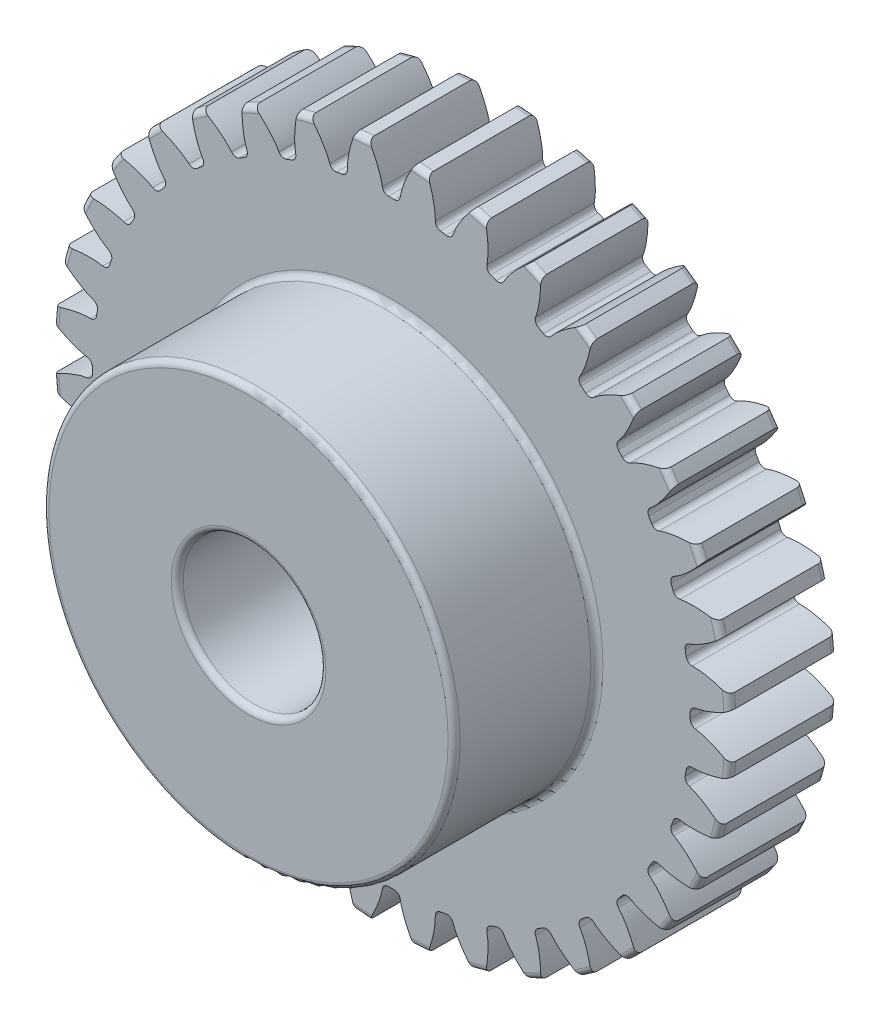
SolidWorks part; units mm, degrees
ref_plane "Front Plane" through (0, 0, 0) normal (0, 0, 1) x (1, 0, 0)
ref_plane "Top Plane" through (0, 0, 0) normal (0, 1, 0) x (1, 0, 0)
ref_plane "Right Plane" through (0, 0, 0) normal (1, 0, 0) x (0, 0, -1)
sketch "Sketch1" plane through (0, 0, 0) normal (0, 0, 1) x (1, 0, 0)
  line L0 (0, 0) -> (0, 14.2875) construction
  line L1 (-4.5919, 15.9588) -> (4.5919, 12.6162) construction
  circle A0 centre (0, 0) radius 13.2953 construction
  circle A1 centre (0, 0) radius 15.0813 construction
  circle A2 centre (0, 0) radius 14.2875 construction
  circle A3 centre (0, 0) radius 13.4259 construction
  circle A4 centre (0, 0) radius 3.175 construction
  circle A5 centre (0, 0) radius 9.144 construction
  point P8 (406.4, 0)
  point P13 (457.2, 0)
  dimension "OD | Outside Diameter" = 30.1625
  dimension "Root Diameter" = 26.5906
  dimension "Gear Pitch Diameter" = 28.575
  dimension "Base Diameter" = 26.8517
  dimension "For Shaft Diameter" = 6.35
  dimension "Hub Diameter" = 18.288
  dimension "Pressure Angle" = 20
  dimension "Number of Teeth" = 914.4
  dimension "Gear Pitch | Diametral Pitch" = 812.8
sketch "Sketch2" plane through (0, 0, 0) normal (1, 0, 0) x (0, 0, -1)
  line L0 (-5.5626, 0) -> (5.5626, 0) construction
  line L1 (-5.5626, 15.0813) -> (5.5626, 15.0813) construction
  point P2 (0, 15.0813)
  point P4 (0.7874, 0)
  point P6 (0.7874, 15.0813)
  dimension "Overall Width" = 11.1252
  dimension "Hub Width" = 6.35
  dimension "Face Width" = 4.7752
sketch "Sketch3" plane through (0, 0, 0) normal (0, 0, 1) x (1, 0, 0)
  circle A0 centre (0, 0) radius 15.0813
  circle A1 centre (0, 0) radius 15.0813 construction
extrude "Boss-Extrude1" add sketch "Sketch3" against normal up to vertex (5.5626 mm away) and the other way up to vertex (5.5626 mm away) up to point (0, 0, -5.5626) other way up to point (0, 0, 5.5626)
sketch "Sketch5" plane through (0, 0, 0) normal (1, 0, 0) x (0, 0, -1)
  line L1 (-5.5626, 15.0813) -> (0.7874, 15.0813)
  line L2 (-5.5626, 15.0813) -> (-5.5626, 9.144)
  line L3 (-5.5626, 9.144) -> (0.7874, 9.144)
  line L4 (0.7874, 15.0813) -> (0.7874, 9.144)
  line L11 (5.5626, 3.175) -> (-5.5626, 3.175)
  line L12 (5.5626, 3.175) -> (5.5626, 0)
  line L13 (5.5626, 0) -> (-5.5626, 0)
  line L14 (-5.5626, 3.175) -> (-5.5626, 0)
  point P5 (0, 3.175)
  point P12 (0, 9.144)
revolve "Cut-Revolve1" cut sketch "Sketch5" angle 360 about L0
fillet "Fillet2" radius 0.2663 6 edges at (15.0813, 0, -5.5626) (3.175, 0, -5.5626) (3.175, 0, 5.5626) (9.144, 0, -0.7874) (15.0813, 0, -0.7874) (9.144, 0, 5.5626)
sketch "Sketch4" plane through (0, 0, 0) normal (0, 0, 1) x (1, 0, 0)
  line L0 (0, 0) -> (13.2898, 0.3819) construction
  line L2 (0, 0) -> (13.2898, -0.3819) construction
  line L4 (13.2898, 0.3819) -> (13.4203, 0.3857)
  line L5 (13.4203, -0.3857) -> (13.2898, -0.3819)
  arc A0 (13.2898, 0.3819) -> (13.2898, -0.3819) centre (0, 0) cw
  arc A3 (15.0469, 1.0166) -> (15.0469, -1.0166) centre (0, 0) cw
  circle A4 centre (0, 0) radius 15.0813 construction
  spline S0 degree 4 poles (13.4203, 0.3857) (13.4229, 0.3858) (13.4302, 0.3861) (13.4439, 0.3872) (13.4664, 0.3894) (13.4949, 0.3929) (13.5317, 0.3983) (13.5751, 0.4057) (13.6226, 0.415) (13.6743, 0.4262) (13.7257, 0.4385) (13.777, 0.4518) (13.8279, 0.4659) (13.8896, 0.484) (13.9633, 0.5072) (14.0493, 0.5364) (14.1466, 0.572) (14.2454, 0.611) (14.3424, 0.6516) (14.4401, 0.6952) (14.5343, 0.7391) (14.6319, 0.7873) (14.7218, 0.8331) (14.822, 0.8873) (14.9028, 0.9319) (15.0089, 0.9937) (15.0715, 1.0311) (15.1445, 1.076) (15.1768, 1.0964) (15.1967, 1.109) knots 0 0 0 0 0 0.005377 0.015084 0.028532 0.04661 0.064855 0.092111 0.119476 0.146842 0.174209 0.201575 0.228941 0.256307 0.307035 0.361767 0.4165 0.471232 0.525964 0.580697 0.635429 0.690161 0.744894 0.799626 0.854358 0.909091 0.954545 1 1 1 1 1 construction
  spline S1 degree 4 poles (13.4203, 0.3857) (13.4229, 0.3858) (13.4302, 0.3861) (13.4439, 0.3872) (13.4664, 0.3894) (13.4949, 0.3929) (13.5317, 0.3983) (13.5751, 0.4057) (13.6226, 0.415) (13.6743, 0.4262) (13.7257, 0.4385) (13.777, 0.4518) (13.8279, 0.4659) (13.8896, 0.484) (13.9633, 0.5072) (14.0493, 0.5364) (14.1466, 0.572) (14.2454, 0.611) (14.3424, 0.6516) (14.4401, 0.6952) (14.5343, 0.7391) (14.6319, 0.7873) (14.7218, 0.8331) (14.822, 0.8873) (14.9028, 0.9319) (14.9859, 0.9803) (15.0263, 1.0042) (15.0469, 1.0166) knots 0 0 0 0 0 0.005377 0.015084 0.028532 0.04661 0.064855 0.092111 0.119476 0.146842 0.174209 0.201575 0.228941 0.256307 0.307035 0.361767 0.4165 0.471232 0.525964 0.580697 0.635429 0.690161 0.744894 0.799626 0.854358 0.909091 0.909091 0.909091 0.909091 0.909091
  spline S2 degree 4 poles (13.4203, -0.3857) (13.4229, -0.3858) (13.4302, -0.3861) (13.4439, -0.3872) (13.4664, -0.3894) (13.4949, -0.3929) (13.5317, -0.3983) (13.5751, -0.4057) (13.6226, -0.415) (13.6743, -0.4262) (13.7257, -0.4385) (13.777, -0.4518) (13.8279, -0.4659) (13.8896, -0.484) (13.9633, -0.5072) (14.0493, -0.5364) (14.1466, -0.572) (14.2454, -0.611) (14.3424, -0.6516) (14.4401, -0.6952) (14.5343, -0.7391) (14.6319, -0.7873) (14.7218, -0.8331) (14.822, -0.8873) (14.9028, -0.9319) (15.0089, -0.9937) (15.0715, -1.0311) (15.1445, -1.076) (15.1768, -1.0964) (15.1967, -1.109) knots 0 0 0 0 0 0.005377 0.015084 0.028532 0.04661 0.064855 0.092111 0.119476 0.146842 0.174209 0.201575 0.228941 0.256307 0.307035 0.361767 0.4165 0.471232 0.525964 0.580697 0.635429 0.690161 0.744894 0.799626 0.854358 0.909091 0.954545 1 1 1 1 1 construction
  spline S3 degree 4 poles (13.4203, -0.3857) (13.4229, -0.3858) (13.4302, -0.3861) (13.4439, -0.3872) (13.4664, -0.3894) (13.4949, -0.3929) (13.5317, -0.3983) (13.5751, -0.4057) (13.6226, -0.415) (13.6743, -0.4262) (13.7257, -0.4385) (13.777, -0.4518) (13.8279, -0.4659) (13.8896, -0.484) (13.9633, -0.5072) (14.0493, -0.5364) (14.1466, -0.572) (14.2454, -0.611) (14.3424, -0.6516) (14.4401, -0.6952) (14.5343, -0.7391) (14.6319, -0.7873) (14.7218, -0.8331) (14.822, -0.8873) (14.9028, -0.9319) (14.9859, -0.9803) (15.0263, -1.0042) (15.0469, -1.0166) knots 0 0 0 0 0 0.005377 0.015084 0.028532 0.04661 0.064855 0.092111 0.119476 0.146842 0.174209 0.201575 0.228941 0.256307 0.307035 0.361767 0.4165 0.471232 0.525964 0.580697 0.635429 0.690161 0.744894 0.799626 0.854358 0.909091 0.909091 0.909091 0.909091 0.909091
  dimension "D1" = 26.5906
extrude "Cut-Extrude1" cut sketch "Sketch4" against normal through all both and the other way through all
fillet "Fillet1" radius 0.2663 2 edges at (13.2898, -0.3819, -3.175) (13.2898, 0.3819, -3.175)
pattern_circular "CirPattern1" count 36 over 360 about axis through (0, 0, 5.5626) along (0, 0, -1) of "Cut-Extrude1", "Fillet1"
ref_axis "Axis1" through (0, 0, -5.2963) along (0, 0, 1)
equation "\"Root Diameter@Sketch1\"=\"Root Diameter\""
equation "\"OD | Outside Diameter@Sketch1\"=\"Outside Diameter\""
equation "\"D1@CirPattern1\"=\"Number of Teeth\""
equation "\"Diametral Pitch\"=32"
equation "\"Number of Teeth\"= 36"
equation "\"Pressure Angle\"=20"
equation "\"Pitch Diameter\"= \"Number of Teeth\" / \"Diametral Pitch\""
equation "\"Base Diameter\"= \"Pitch Diameter\" * cos ( \"Pressure Angle\" )"
equation "\"Outside Diameter\"= ( \"Number of Teeth\" + 2 ) / \"Diametral Pitch\""
equation "\"Dedendum\"= 1.25 / \"Diametral Pitch\""
equation "\"Root Diameter\"= \"Pitch Diameter\" - ( 2 * \"Dedendum\" )"
equation "\"Pitch Angle\"= 360deg / \"Number of Teeth\""
equation "\"Alpha\"= sqr ( \"Pitch Diameter\" ^ 2 - \"Base Diameter\" ^ 2 ) / \"Base Diameter\" * 180 / PI - \"Pressure Angle\""
equation "\"Beta\"= ( \"Pitch Angle\" / 4 - \"Alpha\" )"
equation "\"Phi\"= sqr ( ( \"Outside Diameter\" / 2 ) ^ 2 - ( \"Base Diameter\" / 2 ) ^ 2 ) / ( \"Base Diameter\" / 2 )"
equation "\"Addendum\"= 1 / \"Diametral Pitch\""
equation "\"WorkingDepth\"= 2 / \"Diametral Pitch\""
equation "\"WholeDepth\"= 2.25 / \"Diametral Pitch\""
equation "\"Clearance\"= 0.25 / \"Diametral Pitch\""
equation "\"ToothThickness\"= ( pi * 2 ) / \"Diametral Pitch\""
equation "\"CircularPitch\"= pi / \"Diametral Pitch\""
equation "\"Number of Teeth@Sketch1\"=\"Number of Teeth\""
equation "\"Gear Pitch | Diametral Pitch@Sketch1\"=\"Diametral Pitch\""
equation "\"Pressure Angle@Sketch1\"=\"Pressure Angle\""
equation "\"Gear Pitch Diameter@Sketch1\"=\"Pitch Diameter\""
equation "\"Base Diameter@Sketch1\"=\"Base Diameter\""
equation "\"Fillet\"= \"Clearance\" * cos ( \"Pressure Angle\" ) * tan ( ( 90 + \"Pressure Angle\" ) / 2 )"
equation "\"D1@Fillet1\"=\"Fillet\""
equation "\"D1@Sketch4\"=if( \"Base Diameter\">\"Root Diameter\",\"Root Diameter\",\"Base Diameter\"-.00001)"
equation "\"D1@Fillet2\"=\"Fillet\""
